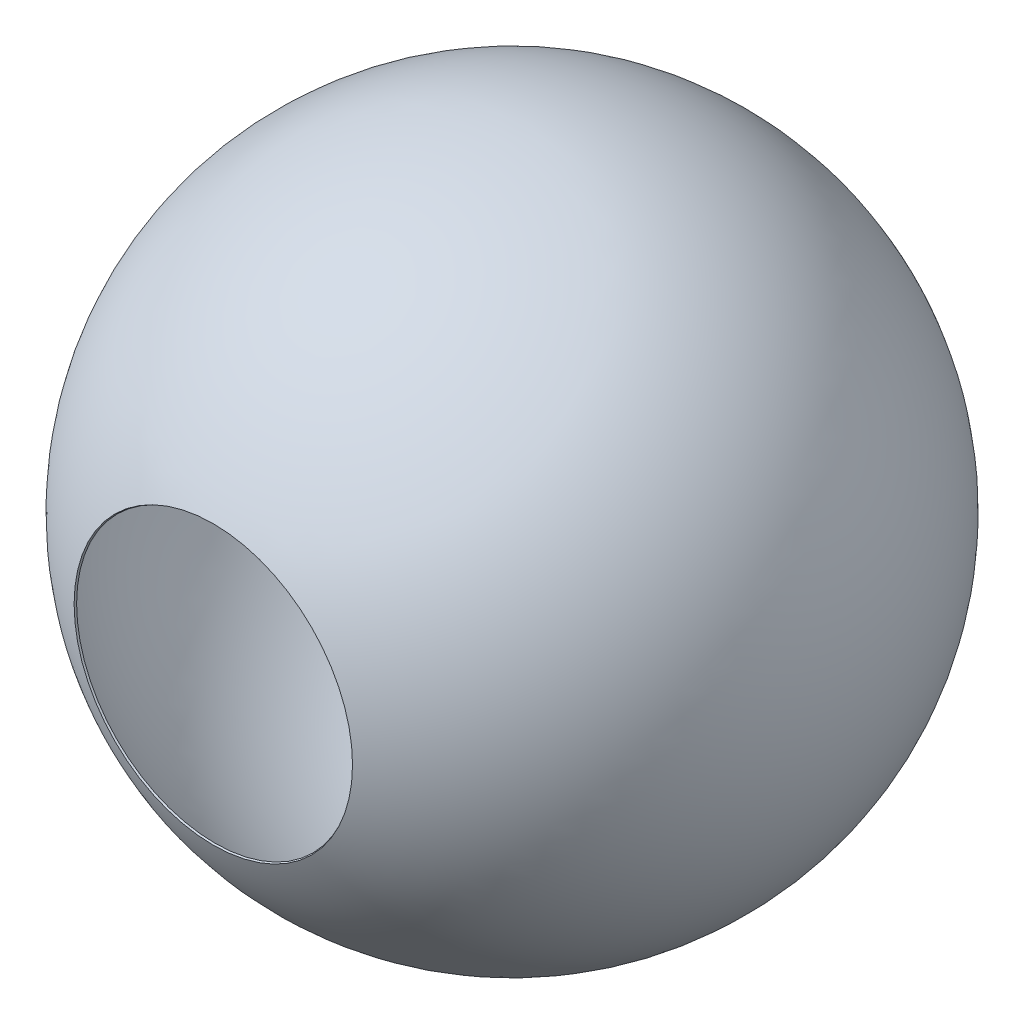
SolidWorks part; units mm, degrees
ref_plane "Front Plane" through (0, 0, 0) normal (0, 0, 1) x (1, 0, 0)
ref_plane "Top Plane" through (0, 0, 0) normal (0, 1, 0) x (1, 0, 0)
ref_plane "Right Plane" through (0, 0, 0) normal (1, 0, 0) x (0, 0, -1)
sketch "Sketch1" plane through (0, 0, 0) normal (1, 0, 0) x (0, 0, -1)
  line L0 (528.5016, 124.6399) -> (528.5016, 0)
  line L3 (-495, 230.6517) -> (-495, 0) construction
  line L4 (-492.1901, 229.3424) -> (0, 0) construction
  line L5 (-495, 230.6517) -> (-492.1901, 229.3424)
  line L6 (-495, 0) -> (531.6016, 0) construction
  line L7 (531.6016, 125) -> (531.6016, 0)
  line L8 (528.5016, 0) -> (531.6016, 0)
  arc A0 (531.6016, 125) -> (-495, 230.6517) centre (0, 0) ccw
  arc A1 (528.5016, 124.6399) -> (-492.1901, 229.3424) centre (0, 0) ccw
  point P1 (0, 0)
  point P5 (0, 0)
  point P8 (0, 0)
  dimension "D1" = 546.1
  dimension "D2" = 543
  dimension "D3" = 495
  dimension "D4" = 125
  dimension "D5" = 3.1
revolve "Shell" add sketch "Sketch1" angle 360 about L6
sketch "Sketch3" plane through (0, 0, 0) normal (0, 0, 1) x (1, 0, 0)
  line L0 (-356.5753, -20.7815) -> (269.657, 26.3052) construction
  line L1 (0, 543) -> (0, -543) construction
  line L2 (0, 0) -> (271.5, 470.2518) construction
  line L3 (0, 0) -> (-271.5, 470.2518) construction
  line L4 (-543, 0) -> (543, 0) construction
  line L5 (0, 0) -> (457.9616, -291.7537) construction
  line L6 (0, 0) -> (-457.9616, -291.7537) construction
  circle A0 centre (0, 0) radius 543
  dimension "D1" = 1086
  dimension "D2" = 60
  dimension "D3" = 115
